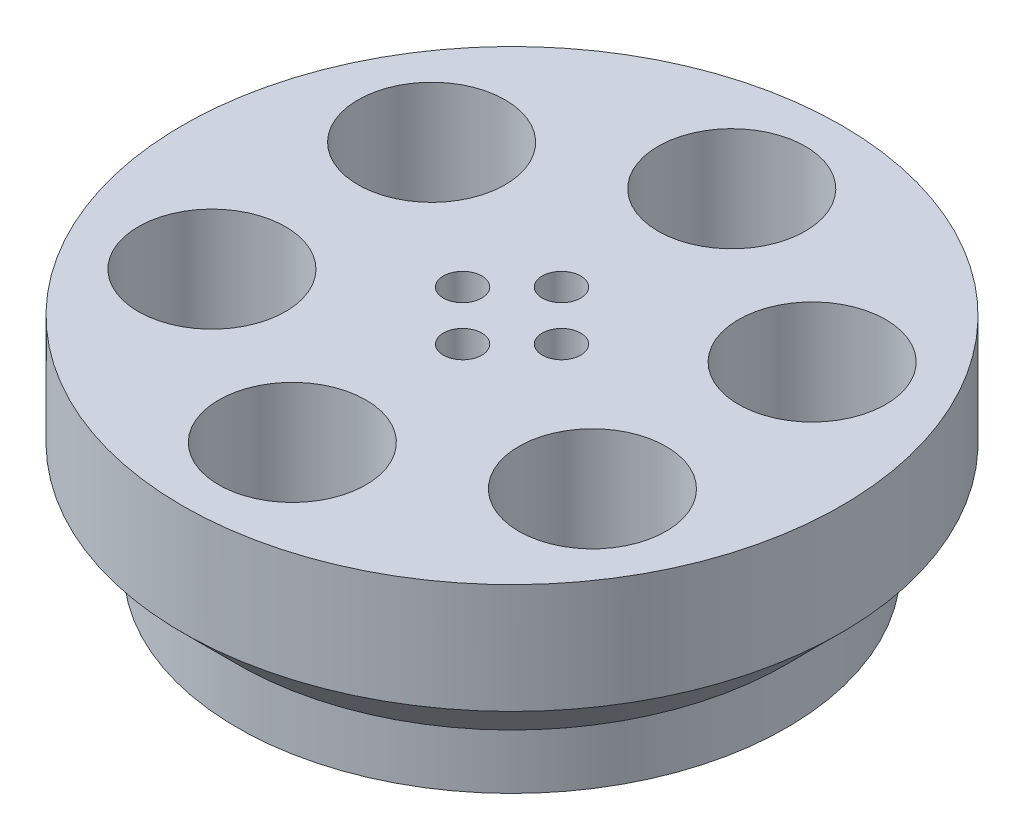
SolidWorks part; units mm, degrees
material "ABS PC"
ref_plane "Front Plane" through (0, 0, 0) normal (0, 0, 1) x (1, 0, 0)
ref_plane "Top Plane" through (0, 0, 0) normal (0, 1, 0) x (1, 0, 0)
ref_plane "Right Plane" through (0, 0, 0) normal (1, 0, 0) x (0, 0, -1)
sketch "Sketch1" plane through (0, 0, 0) normal (0, 1, 0) x (1, 0, 0)
  circle A0 centre (0, 0) radius 30
  dimension "D1" = 60
extrude "Boss-Extrude1" add sketch "Sketch1" along normal blind 20
sketch "Sketch2" plane through (0, 20, 0) normal (0, 1, 0) x (1, 0, 0)
  line L0 (0, -11) -> (0, 11) construction
  line L1 (-11, 0) -> (11, 0) construction
  line L2 (0, 26.7) -> (16.0728, 26.7) construction
  line L3 (0, 30) -> (15.4299, 30) construction
  circle A0 centre (0, 20) radius 6.7
  circle A1 centre (0, 0) radius 30 construction
  dimension "D1" = 13.4
  dimension "D2" = 20
  dimension "D3" = 3.3
extrude "Cut-Extrude1" cut sketch "Sketch2" against normal blind 10
sketch "Sketch3" plane through (0, 10, 0) normal (0, 1, 0) x (1, 0, 0)
  circle A0 centre (0, 20) radius 2
  dimension "D1" = 4
extrude "Cut-Extrude2" cut sketch "Sketch3" against normal blind 35
pattern_circular "CirPattern1" count 6 over 360 about axis through (0, 20, 0) along (0, 1, 0) of "Cut-Extrude1", "Cut-Extrude2"
sketch "Sketch6" plane through (0, 20, 0) normal (0, 1, 0) x (1, 0, 0)
  circle A0 centre (4.5, 0) radius 1.75
  dimension "D2" = 3.5
  dimension "D1" = 4.5
extrude "Cut-Extrude4" cut sketch "Sketch6" against normal blind 45
pattern_circular "CirPattern3" count 4 over 360 about axis through (0, 20, 0) along (0, 1, 0) of "Cut-Extrude4"
sketch "Sketch7" plane through (0, 0, 0) normal (0, 0, 1) x (1, 0, 0)
  line L0 (-25, 0) -> (-25, 5)
  line L1 (-30, 0) -> (30, 0) construction
  line L2 (-25, 5) -> (-30, 10)
  line L3 (-30, 20) -> (-30, 0) construction
  line L4 (-25, 0) -> (-30, 0)
  line L5 (-30, 0) -> (-30, 10)
  line L6 (0, 0) -> (0, 26.2682) construction
  dimension "D1" = 5
  dimension "D2" = 10
  dimension "D3" = 5
revolve "Cut-Revolve1" cut sketch "Sketch7" angle 360 about L6
